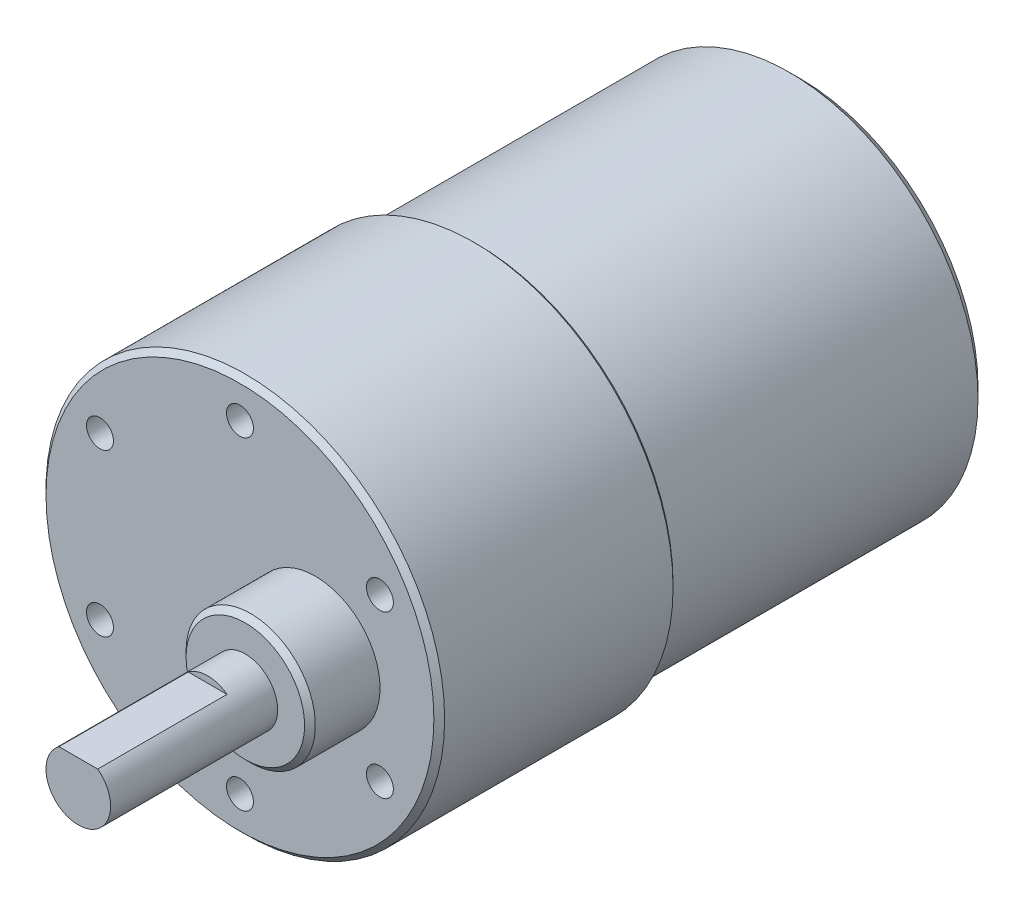
SolidWorks part; units mm, degrees
ref_plane "Front Plane" through (0, 0, 0) normal (0, 0, 1) x (1, 0, 0)
ref_plane "Top Plane" through (0, 0, 0) normal (0, 1, 0) x (1, 0, 0)
ref_plane "Right Plane" through (0, 0, 0) normal (1, 0, 0) x (0, 0, -1)
sketch "Sketch2" plane through (0, 0, 0) normal (0, 0, 1) x (1, 0, 0)
  circle A0 centre (0, 0) radius 17.5
  dimension "D1" = 35
extrude "Boss-Extrude1" add sketch "Sketch2" along normal blind 30
sketch "Sketch3" plane through (0, 0, 30) normal (0, 0, 1) x (1, 0, 0)
  circle A0 centre (0, 0) radius 18.5
  dimension "D1" = 37
extrude "Boss-Extrude2" add sketch "Sketch3" along normal blind 22
hole_wizard "M3x0.5 Tapped Hole1" positions "Sketch5" profile "Sketch4" tap size "M3x0.5" standard "ANSI Metric"
sketch "Sketch5" plane through (0, 0, 52) normal (0, 0, 1) x (1, 0, 0)
  line L1 (12.9904, -7.5) -> (12.9904, 7.5)
  line L2 (12.9904, 7.5) -> (0, 15)
  line L3 (0, 15) -> (-12.9904, 7.5)
  line L4 (-12.9904, 7.5) -> (-12.9904, -7.5)
  line L5 (-12.9904, -7.5) -> (0, -15)
  line L6 (0, -15) -> (12.9904, -7.5)
  circle A0 centre (0, 0) radius 12.9904 construction
  point P3 (12.9904, -7.5)
  point P4 (12.9904, 7.5)
  point P5 (0, 15)
  point P6 (-12.9904, 7.5)
  point P7 (-12.9904, -7.5)
  point P8 (0, -15)
  dimension "D1" = 15
sketch "Sketch4" plane through (12.9904, -7.5, 52) normal (1, 0, 0) x (0, -1, 0)
  line L0 (0, 0) -> (0, 8.2511)
  line L1 (0, 8.2511) -> (1.25, 7.5)
  line L2 (1.25, 7.5) -> (1.25, 0)
  line L5 (1.25, 0) -> (0, 0)
  line L10 (0, 8.2511) -> (-1.25, 7.5) construction
  line L11 (0, -6.35) -> (0, 107.95) construction
  dimension "Tap Drill Dia." = 2.5
  dimension "Tap Drill Depth" = 7.5
  dimension "Drill Angle" = 118
cosmetic thread "Hole Thread1" parameters "D1"=6, "D2"=3
cosmetic thread "Hole Thread2" parameters "D1"=6, "D2"=3
cosmetic thread "Hole Thread3" parameters "D1"=6, "D2"=3
cosmetic thread "Hole Thread4" parameters "D1"=6, "D2"=3
cosmetic thread "Hole Thread5" parameters "D1"=6, "D2"=3
cosmetic thread "Hole Thread6" parameters "D1"=6, "D2"=3
sketch "Sketch6" plane through (0, 0, 52) normal (0, 0, 1) x (1, 0, 0)
  circle A0 centre (7, 0) radius 6
  point P2 (0, 0)
  dimension "D2" = 12
  dimension "D1" = 7
extrude "Boss-Extrude3" add sketch "Sketch6" along normal blind 6.5
sketch "Sketch8" plane through (0, 0, 58.5) normal (0, 0, 1) x (1, 0, 0)
  circle A0 centre (7, 0) radius 6 construction
  circle A1 centre (7, 0) radius 6
  circle A2 centre (7, 0) radius 3
  dimension "D1" = 6
extrude "Boss-Extrude4" add sketch "Sketch8" along normal blind 3.5 contours A2 region at (7, 0, 58.5)
sketch "Sketch9" plane through (0, 0, 62) normal (0, 0, 1) x (1, 0, 0)
  line L0 (5.2, 2.4) -> (8.8, 2.4)
  circle A0 centre (7, 0) radius 3
  point P0 (7, 0)
  point P6 (7, -3)
  circle M1 centre (7, 0) radius 3
  dimension "D2" = 6
  dimension "D1" = 5.4
extrude "Boss-Extrude5" add sketch "Sketch9" along normal blind 12 contours L0 M1 region at (7, -0.1451, 62)
chamfer "Chamfer1" distance 0.5 angle 45 1 edges at (18.5, 0, 52)
chamfer "Chamfer2" distance 0.5 angle 45 1 edges at (13, 0, 58.5)
chamfer "Chamfer3" distance 0.3 angle 45 1 edges at (18.5, 0, 30)
chamfer "Chamfer4" distance 1 angle 45 1 edges at (17.5, 0, 0)
